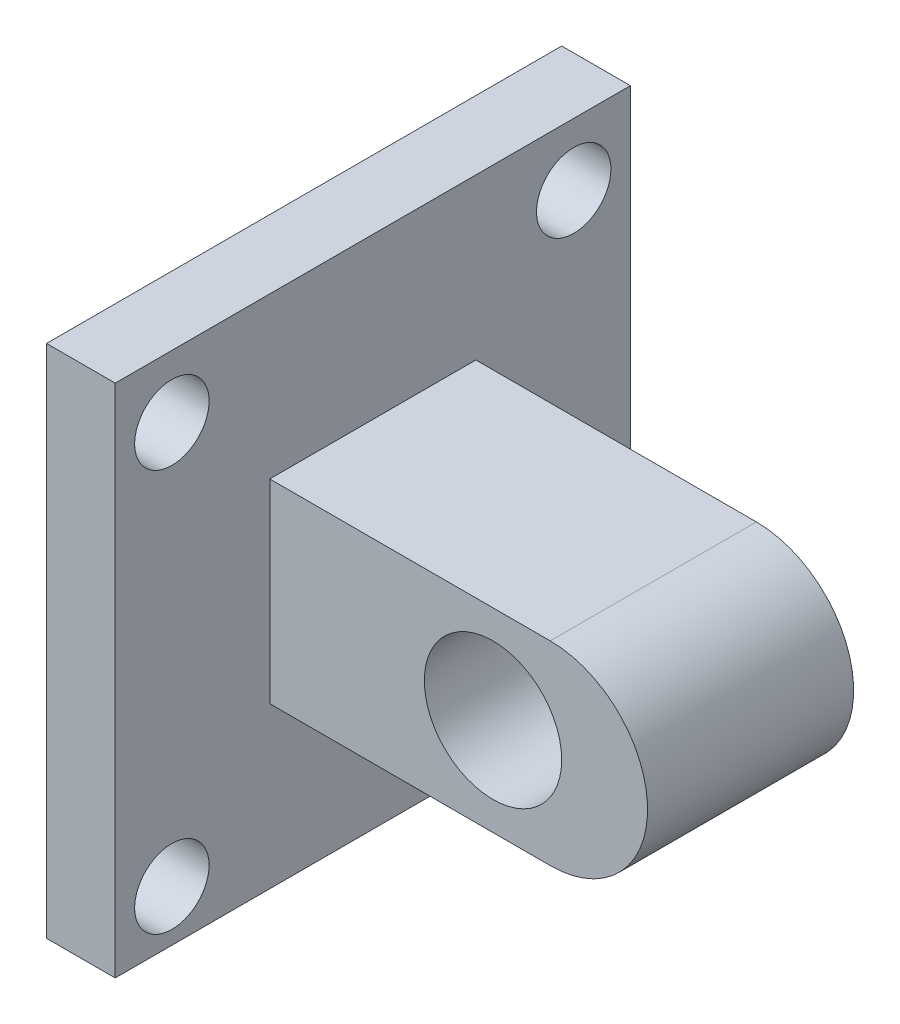
SolidWorks part; units mm, degrees
other "DetailItem1"
other "Weld Folder"
other "Weld Bead1"
ref_plane "Płaszczyzna przednia" through (0, 0, 0) normal (0, 0, 1) x (1, 0, 0)
ref_plane "Płaszczyzna górna" through (0, 0, 0) normal (0, 1, 0) x (1, 0, 0)
ref_plane "Płaszczyzna prawa" through (0, 0, 0) normal (1, 0, 0) x (0, 0, -1)
sketch "Szkic1" plane through (0, 0, 0) normal (0, 0, 1) x (1, 0, 0)
  line L0 (-849.5535, 602.1198) -> (-849.5535, 512.1198)
  line L1 (-849.5535, 512.1198) -> (-837.5535, 512.1198)
  line L2 (-837.5535, 512.1198) -> (-837.5535, 602.1198)
  line L3 (-837.5535, 602.1198) -> (-849.5535, 602.1198)
  line L4 (-837.5535, 574.1198) -> (-788.5535, 574.1198)
  line L6 (-788.5535, 540.1198) -> (-837.5535, 540.1198)
  circle A0 centre (-798.5535, 557.1198) radius 12
  arc A1 (-788.5535, 574.1198) -> (-788.5535, 540.1198) centre (-788.5535, 557.1198) cw
  point P11 (-771.5535, 557.1198)
  point P12 (-837.5535, 557.1198)
  dimension "D4" = 24
  dimension "D1" = 34
  dimension "D2" = 12
  dimension "D3" = 39
  dimension "D5" = 27
  dimension "D6" = 90
extrude "Dodanie-wyciągnięcie3" add sketch "Szkic1" along normal blind 18 and the other way blind 18 contours A1 L4 L2 L6 A0 region at (-813.0535, 573.3774, 0)
extrude "Dodanie-wyciągnięcie4" add sketch "Szkic1<6>" along normal blind 45 and the other way blind 45 contours L2 L3 L0 L1 region at (-843.5535, 557.1198, 0)
sketch "Szkic1<6>" plane through (0, 0, 0) normal (0, 0, 1) x (1, 0, 0) same geometry as "Szkic1"
ref_plane "Płaszczyzna2" through (-837.5535, 0, 0) normal (1, 0, 0) x (0, 0, -1)
sketch "Szkic46" plane through (0, 0, 45) normal (0, 0, 1) x (1, 0, 0)
  line L0 (-843.5535, 602.1198) -> (-843.5535, 512.1198)
  line L1 (-837.5535, 602.1198) -> (-849.5535, 602.1198) construction
  line L2 (-849.5535, 512.1198) -> (-837.5535, 512.1198) construction
sketch "Sketch5" plane through (-837.5535, 0, 0) normal (1, 0, 0) x (0, 0, -1)
  line L0 (-45, 602.1198) -> (-35.1005, 591.2203)
  line L1 (-45, 512.1198) -> (-35.1005, 521.0193)
  line L2 (45, 602.1198) -> (35.1005, 591.2203)
  line L3 (45, 512.1198) -> (35.1005, 521.0193)
  circle A0 centre (-35.1005, 591.2203) radius 6.5
  circle A1 centre (35.1005, 591.2203) radius 6.5
  circle A2 centre (35.1005, 521.0193) radius 6.5
  circle A3 centre (-35.1005, 521.0193) radius 6.5
extrude "Cut-Extrude1" cut sketch "Sketch5" against normal blind 12 contours A0 | A1 | A2 | A3 region at (-837.5535, 585.4447, 37.6571) region at (-837.5535, 588.6638, -29.3249) region at (-837.5535, 518.7581, -40.998) region at (-837.5535, 515.1218, 32.8393)
